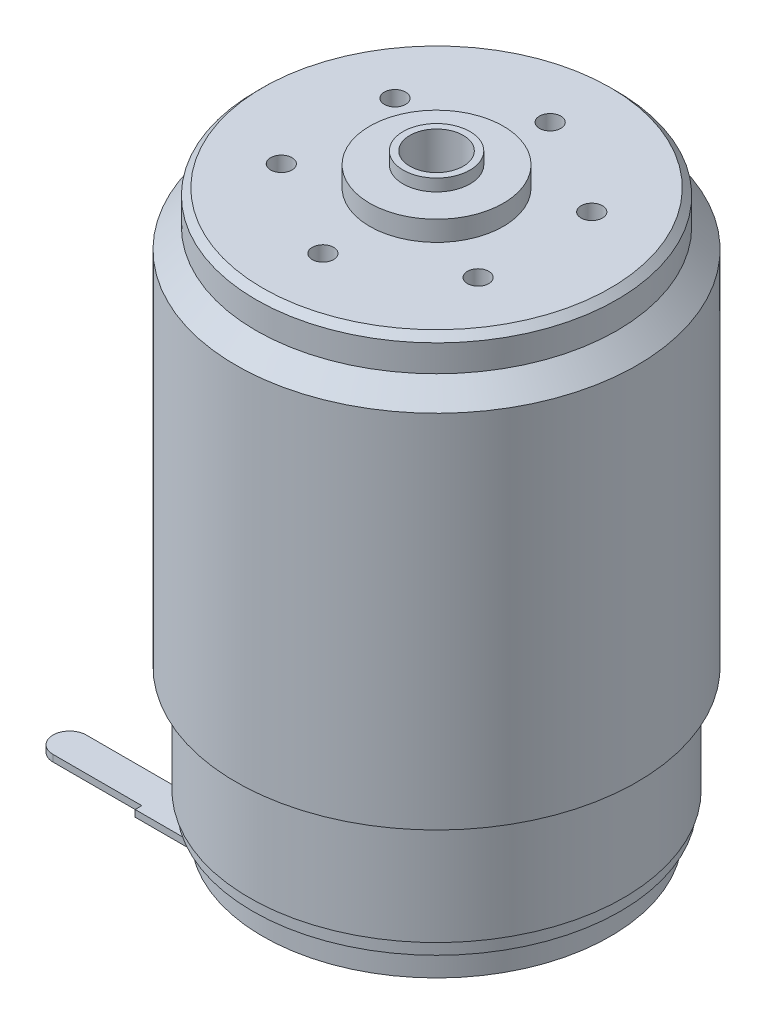
SolidWorks part; units mm, degrees
ref_plane "Face" through (0, 0, 0) normal (0, 0, 1) x (1, 0, 0)
ref_plane "Dessus" through (0, 0, 0) normal (0, 1, 0) x (1, 0, 0)
ref_plane "Droite" through (0, 0, 0) normal (1, 0, 0) x (0, 0, -1)
sketch "Esquisse1" plane through (0, 0, 0) normal (0, 1, 0) x (1, 0, 0)
  circle A0 centre (0, 0) radius 15
  dimension "D1" = 30
extrude "Extrusion1" add sketch "Esquisse1" along normal blind 42
sketch "Esquisse2" plane through (0, 42, 0) normal (0, 1, 0) x (1, 0, 0)
  circle A0 centre (0, 0) radius 13.5
  dimension "D1" = 27
extrude "Enlèv. mat.-Extru.1" cut sketch "Esquisse2" against normal blind 4 flip side to cut
sketch "Esquisse3" plane through (0, 0, 0) normal (0, -1, 0) x (1, 0, 0)
  circle A0 centre (0, 0) radius 13
  dimension "D1" = 26
extrude "Enlèv. mat.-Extru.2" cut sketch "Esquisse3" against normal blind 2 flip side to cut
sketch "Esquisse4" plane through (0, 2, 0) normal (0, -1, 0) x (1, 0, 0)
  circle A0 centre (0, 0) radius 13.75
  dimension "D1" = 27.5
extrude "Enlèv. mat.-Extru.3" cut sketch "Esquisse4" against normal blind 1 flip side to cut
sketch "Esquisse5" plane through (0, 3, 0) normal (0, -1, 0) x (1, 0, 0)
  circle A0 centre (0, 0) radius 14
  dimension "D1" = 28
extrude "Enlèv. mat.-Extru.4" cut sketch "Esquisse5" against normal blind 8 flip side to cut
chamfer "Chanfrein1" distance 0.5 angle 45 1 edges at (0, 42, 13.5)
chamfer "Chanfrein2" distance 1.5 angle 45 1 edges at (0, 38, 13.5)
sketch "Esquisse6" plane through (0, 42, 0) normal (0, 1, 0) x (1, 0, 0)
  circle A0 centre (0, 0) radius 5
  dimension "D1" = 10
extrude "Extrusion2" add sketch "Esquisse6" along normal blind 1.5
sketch "Esquisse7" plane through (0, 0, 0) normal (0, -1, 0) x (1, 0, 0)
  circle A0 centre (0, 0) radius 5
  dimension "D1" = 10
extrude "Extrusion3" add sketch "Esquisse7" along normal blind 2
sketch "Esquisse8" plane through (0, 43.5, 0) normal (0, 1, 0) x (1, 0, 0)
  circle A0 centre (0, 0) radius 2.5
  dimension "D1" = 5
extrude "Extrusion4" add sketch "Esquisse8" along normal blind 0.9
sketch "Esquisse9" plane through (0, -2, 0) normal (0, -1, 0) x (1, 0, 0)
  circle A0 centre (0, 0) radius 2.5
  dimension "D1" = 5
extrude "Extrusion5" add sketch "Esquisse9" along normal blind 0.9
sketch "Esquisse10" plane through (0, -2.9, 0) normal (0, -1, 0) x (1, 0, 0)
  circle A0 centre (0, 0) radius 1.5
  dimension "D1" = 3
extrude "Enlèv. mat.-Extru.5" cut sketch "Esquisse10" against normal up to next
sketch "Esquisse11" plane through (0, 44.4, 0) normal (0, 1, 0) x (1, 0, 0)
  circle A0 centre (0, 0) radius 2
  dimension "D1" = 4
extrude "Enlèv. mat.-Extru.6" cut sketch "Esquisse11" against normal blind 10
hole_wizard "Trou taraudé M21" positions "Esquisse13" profile "Esquisse12" tap size "M2" standard "ISO"
sketch "Esquisse13" plane through (0, 42, 0) normal (0, 1, 0) x (-1, 0, 0)
  line L0 (0, 8.5) -> (0, -8.5) construction
  line L2 (-7.3612, -4.25) -> (7.3612, 4.25) construction
  line L4 (-7.3612, 4.25) -> (7.3612, -4.25) construction
  circle A0 centre (0, 0) radius 8.5
  point P0 (0, 8.5)
  point P18 (-7.3612, 4.25)
  point P20 (-7.3612, -4.25)
  point P22 (0, -8.5)
  point P24 (7.3612, -4.25)
  point P26 (7.3612, 4.25)
  dimension "D1" = 17
  dimension "D2" = 60
  dimension "D3" = 60
sketch "Esquisse12" plane through (0, 42, 8.5) normal (1, 0, 0) x (0, 0, 1)
  line L0 (0, 0) -> (0, 3.6807)
  line L1 (0, 3.6807) -> (0.8, 3.2)
  line L2 (0.8, 3.2) -> (0.8, 0)
  line L5 (0.8, 0) -> (0, 0)
  line L10 (0, 3.6807) -> (-0.8, 3.2) construction
  line L11 (0, -6.35) -> (0, 107.95) construction
  dimension "Diamètre du trou pour taraudage" = 1.6
  dimension "Profondeur du trou pour taraudage" = 3.2
  dimension "Angle de pointe" = 118
cosmetic thread "Filetage de perçage1" parameters "D1"=2, "D2"=2
cosmetic thread "Filetage de perçage2" parameters "D1"=2, "D2"=2
cosmetic thread "Filetage de perçage3" parameters "D1"=2, "D2"=2
cosmetic thread "Filetage de perçage4" parameters "D1"=2, "D2"=2
cosmetic thread "Filetage de perçage5" parameters "D1"=2, "D2"=2
cosmetic thread "Filetage de perçage6" parameters "D1"=2, "D2"=2
hole_wizard "Trou taraudé M22" positions "Esquisse15" profile "Esquisse14" tap size "M2" standard "ISO"
sketch "Esquisse15" plane through (0, 0, 0) normal (0, -1, 0) x (1, 0, 0)
  line L0 (10, 0) -> (-10, 0) construction
  circle A0 centre (0, 0) radius 10
  point P0 (10, 0)
  point P10 (10, 0)
  point P17 (-10, 0)
  dimension "D1" = 20
sketch "Esquisse14" plane through (10, 0, 0) normal (1, 0, 0) x (0, 0, -1)
  line L0 (0, 0) -> (0, 2.6807)
  line L1 (0, 2.6807) -> (0.8, 2.2)
  line L2 (0.8, 2.2) -> (0.8, 0)
  line L5 (0.8, 0) -> (0, 0)
  line L10 (0, 2.6807) -> (-0.8, 2.2) construction
  line L11 (0, -6.35) -> (0, 107.95) construction
  dimension "Diamètre du trou pour taraudage" = 1.6
  dimension "Profondeur du trou pour taraudage" = 2.2
  dimension "Angle de pointe" = 118
cosmetic thread "Filetage de perçage7" parameters "D1"=1, "D2"=2
cosmetic thread "Filetage de perçage8" parameters "D1"=1, "D2"=2
sketch "Esquisse16" plane through (0, 0, 0) normal (0, -1, 0) x (1, 0, 0)
  line L0 (0, 13) -> (0, -13) construction
  line L1 (13, 0) -> (-13, 0) construction
  line L2 (0, 9.5) -> (-3, 9.5)
  line L3 (0, 6.5) -> (-3, 6.5)
  line L4 (-3, 9.5) -> (-3, 6.5)
  line L5 (-7, 9.55) -> (-7, 6.55)
  line L6 (-7, 6.55) -> (-19.65, 6.55)
  line L7 (-19.65, 9.05) -> (-13, 9.05)
  line L8 (-13, 9.05) -> (-13, 9.55)
  line L9 (-13, 9.55) -> (-7, 9.55)
  line L10 (-13, -9.55) -> (-7, -9.55)
  line L11 (-13, -9.05) -> (-13, -9.55)
  line L12 (-19.65, -9.05) -> (-13, -9.05)
  line L13 (-7, -6.55) -> (-19.65, -6.55)
  line L14 (-7, -9.55) -> (-7, -6.55)
  line L15 (-3, -9.5) -> (-3, -6.5)
  line L16 (0, -6.5) -> (-3, -6.5)
  line L17 (0, -9.5) -> (-3, -9.5)
  circle A0 centre (0, 0) radius 13 construction
  arc A1 (0, 9.5) -> (0, 6.5) centre (0, 8) cw
  circle A2 centre (0, 8) radius 0.75
  arc A3 (-19.65, 6.55) -> (-19.65, 9.05) centre (-19.65, 7.8) cw
  arc A4 (-19.65, -6.55) -> (-19.65, -9.05) centre (-19.65, -7.8) ccw
  circle A5 centre (0, -8) radius 0.75
  arc A6 (0, -9.5) -> (0, -6.5) centre (0, -8) ccw
  dimension "D4" = 1.5
  dimension "D1" = 8
  dimension "D2" = 3
  dimension "D3" = 3
  dimension "D5" = 0.5
  dimension "D6" = 7.8
  dimension "D7" = 19.65
  dimension "D8" = 7
  dimension "D9" = 6
extrude "Extrusion6" add sketch "Esquisse16" along normal blind 0.5
